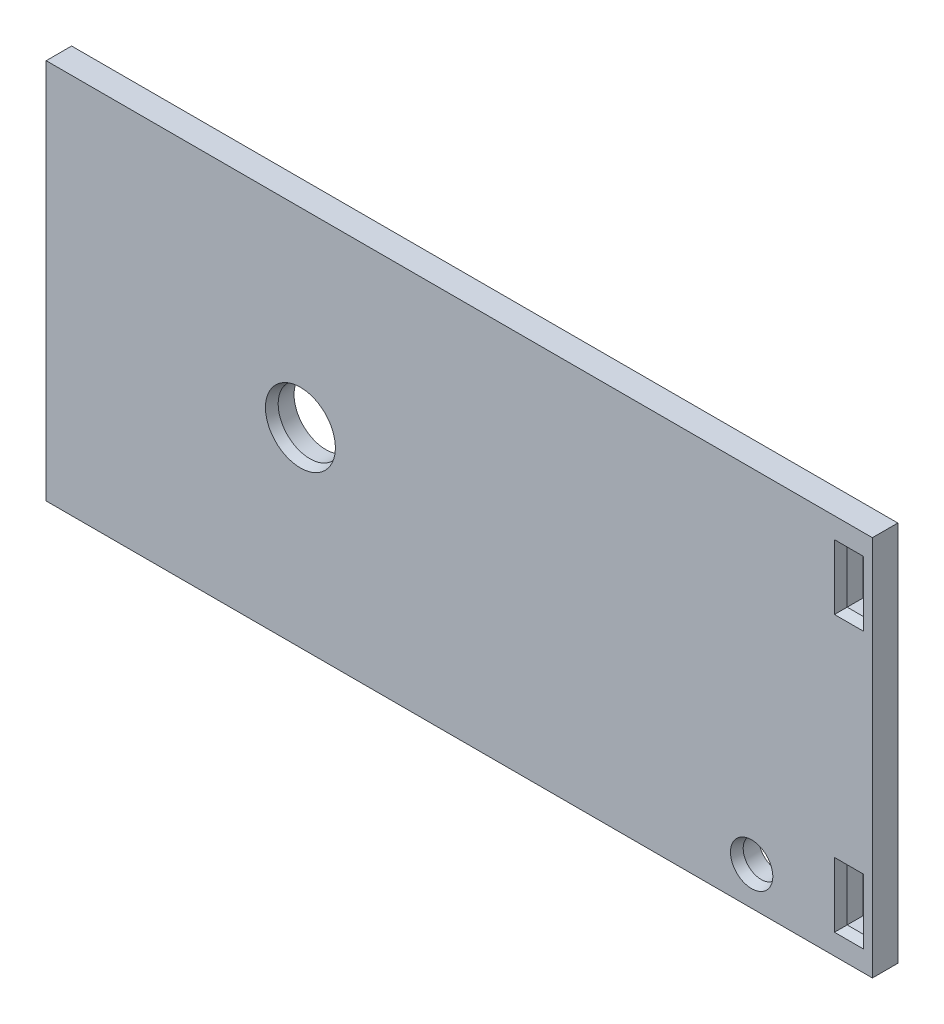
SolidWorks part; units mm, degrees
ref_plane "Front Plane" through (0, 0, 0) normal (0, 0, 1) x (1, 0, 0)
ref_plane "Top Plane" through (0, 0, 0) normal (0, 1, 0) x (1, 0, 0)
ref_plane "Right Plane" through (0, 0, 0) normal (1, 0, 0) x (0, 0, -1)
sketch "Sketch1" plane through (0, 0, 0) normal (0, 0, 1) x (1, 0, 0)
  line L2 (-65, -30) -> (-65, 30)
  line L12 (61.3, 26.25) -> (61.3, 17.05) construction
  line L13 (-65, 30) -> (65, 30)
  line L15 (-65, -30) -> (65, -30)
  line L16 (65, 30) -> (65, -30)
  line L17 (59.535, 26.25) -> (63.065, 26.25)
  line L18 (59.535, 26.25) -> (59.535, 17.05)
  line L19 (59.535, 17.05) -> (63.065, 17.05)
  line L20 (63.065, 26.25) -> (63.065, 17.05)
  line L21 (59.535, -17.05) -> (63.065, -17.05)
  line L22 (59.535, -17.05) -> (59.535, -26.25)
  line L23 (59.535, -26.25) -> (63.065, -26.25)
  line L24 (63.065, -17.05) -> (63.065, -26.25)
  line L25 (61.3, -17.05) -> (61.3, -26.25) construction
  line L26 (63.065, 21.65) -> (59.535, 21.65) construction
  line L27 (63.065, -21.65) -> (59.535, -21.65) construction
  circle A3 centre (-25, 0) radius 5
  circle A4 centre (46, -24) radius 2.83
  circle A6 centre (16, 0) radius 7 construction
  point P2 (0, 30)
  point P9 (65, 0)
  dimension "D6" = 10
  dimension "D4" = 5.66
  dimension "D14" = 14
  dimension "D2" = 60
  dimension "D3" = 130
  dimension "D8" = 24
  dimension "D1" = 9.2
  dimension "D9" = 3.53
  dimension "D10" = 21.65
  dimension "D11" = 21.65
  dimension "D5" = 40
  dimension "D7" = 86.3
  dimension "D12" = 71
  dimension "D13" = 41
extrude "Boss-Extrude1" add sketch "Sketch1" along normal mid plane 4
chamfer "Chamfer1" distance 0.5 distance2 1.5 10 edges at (61.3, 17.05, 2) (59.535, 21.65, 2) (61.3, 26.25, 2) (63.065, 21.65, 2) (-20, 0, 2) (48.83, -24, 2) (61.3, -26.25, 2) (59.535, -21.65, 2) (61.3, -17.05, 2) (63.065, -21.65, 2) first distance on face at (-20, 0, 2)
sketch "Sketch3" plane through (0, 0, -2) normal (0, 0, -1) x (-1, 0, 0)
  line L0 (-61.3, 26.25) -> (-61.3, 17.05) construction
  line L1 (-63.065, 21.65) -> (-59.535, 21.65) construction
  line L2 (-61.3, -17.05) -> (-61.3, -26.25) construction
  line L3 (-59.535, -17.05) -> (-63.065, -17.05) construction
  line L4 (-63.065, -21.65) -> (-59.535, -21.65) construction
equation "\"hole_width\"=3.4"
equation "\"hole_length\"=8.7"
equation "\"pin_hole_height\"=9.2"
equation "\"D1@Sketch1\"=\"pin_hole_height\""
equation "\"pin_hole_width\"=3.53"
equation "\"D9@Sketch1\"=\"pin_hole_width\""
equation "\"wall_thick_ness\"=4"
equation "\"D1@Boss-Extrude1\"=\"wall_thick_ness\""
equation "\"back_boost\"= 7"
equation "\"D5@Sketch1\"=\"back_boost\"+33.00mm"
equation "\"D3@Sketch1\"=123.00mm+\"back_boost\""
